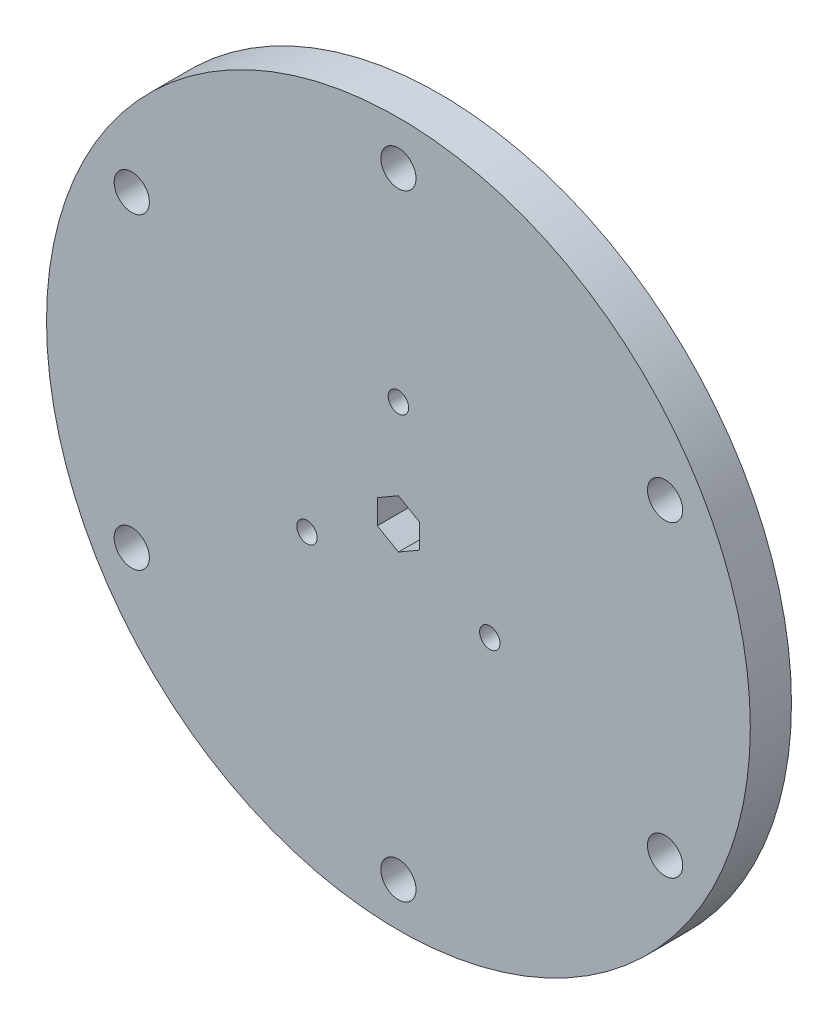
SolidWorks part; units mm, degrees
ref_plane "Front Plane" through (0, 0, 0) normal (0, 0, 1) x (1, 0, 0)
ref_plane "Top Plane" through (0, 0, 0) normal (0, 1, 0) x (1, 0, 0)
ref_plane "Right Plane" through (0, 0, 0) normal (1, 0, 0) x (0, 0, -1)
sketch "Sketch1" plane through (0, 0, 0) normal (0, 0, 1) x (1, 0, 0)
  circle A0 centre (0, 0) radius 50.8
  dimension "D1" = 101.6
extrude "Boss-Extrude1" add sketch "Sketch1" along normal mid plane 5.9436 contours A0
ref_axis "Axis1" through (0, 0, -3.4925) along (0, 0, 1)
sketch "Sketch2" plane through (0, 0, 2.9718) normal (0, 0, 1) x (1, 0, 0)
  circle A0 centre (0, 44.45) radius 2.54
  dimension "D1" = 5.08
  dimension "D2" = 44.45
extrude "Cut-Extrude1" cut sketch "Sketch2" against normal through all
pattern_circular "CirPattern1" count 6 over 360 about axis through (0, 0, -3.4925) along (0, 0, 1) of "Cut-Extrude1"
sketch "Sketch3" plane through (0, 0, 2.9718) normal (0, 0, 1) x (1, 0, 0)
  line L0 (0, 3.5195) -> (3.048, 1.7598)
  line L1 (3.048, -1.7598) -> (0, -3.5195)
  line L2 (0, -3.5195) -> (-3.048, -1.7598)
  line L3 (-3.048, -1.7598) -> (-3.048, 1.7598)
  line L4 (-3.048, 1.7598) -> (0, 3.5195)
  line L5 (3.048, 1.7598) -> (3.048, -1.7598)
  line L6 (0, 0.5666) -> (0, -0.4773) construction
  line L7 (-0.474, 0) -> (1.4174, 0) construction
  dimension "D1" = 6.096
  dimension "D2" = 6.096
extrude "Cut-Extrude2" cut sketch "Sketch3" against normal through all
hole_wizard "#32 (0.116) Diameter Hole1" positions "Sketch5" profile "Sketch6" hole size "#32" standard "ANSI Inch" end condition through all
sketch "Sketch5" plane through (0, 0, 2.9718) normal (0, 0, 1) x (1, 0, 0)
  point P0 (0, 15.24)
  dimension "D1" = 15.24
sketch "Sketch6" plane through (0, 15.24, 2.9718) normal (1, 0, 0) x (0, -1, 0)
  line L0 (0, 0) -> (0, 5.9436)
  line L1 (0, 5.9436) -> (1.4732, 5.9436)
  line L2 (1.4732, 5.9436) -> (1.4732, 0)
  line L5 (1.4732, 0) -> (0, 0)
  line L11 (0, -6.35) -> (0, 107.95) construction
  dimension "Thru Hole Dia." = 2.9464
  dimension "Thru Hole Depth" = 5.9436
pattern_circular "CirPattern2" count 3 over 360 about axis through (0, 0, -3.4925) along (0, 0, 1) of "#32 (0.116) Diameter Hole1"
